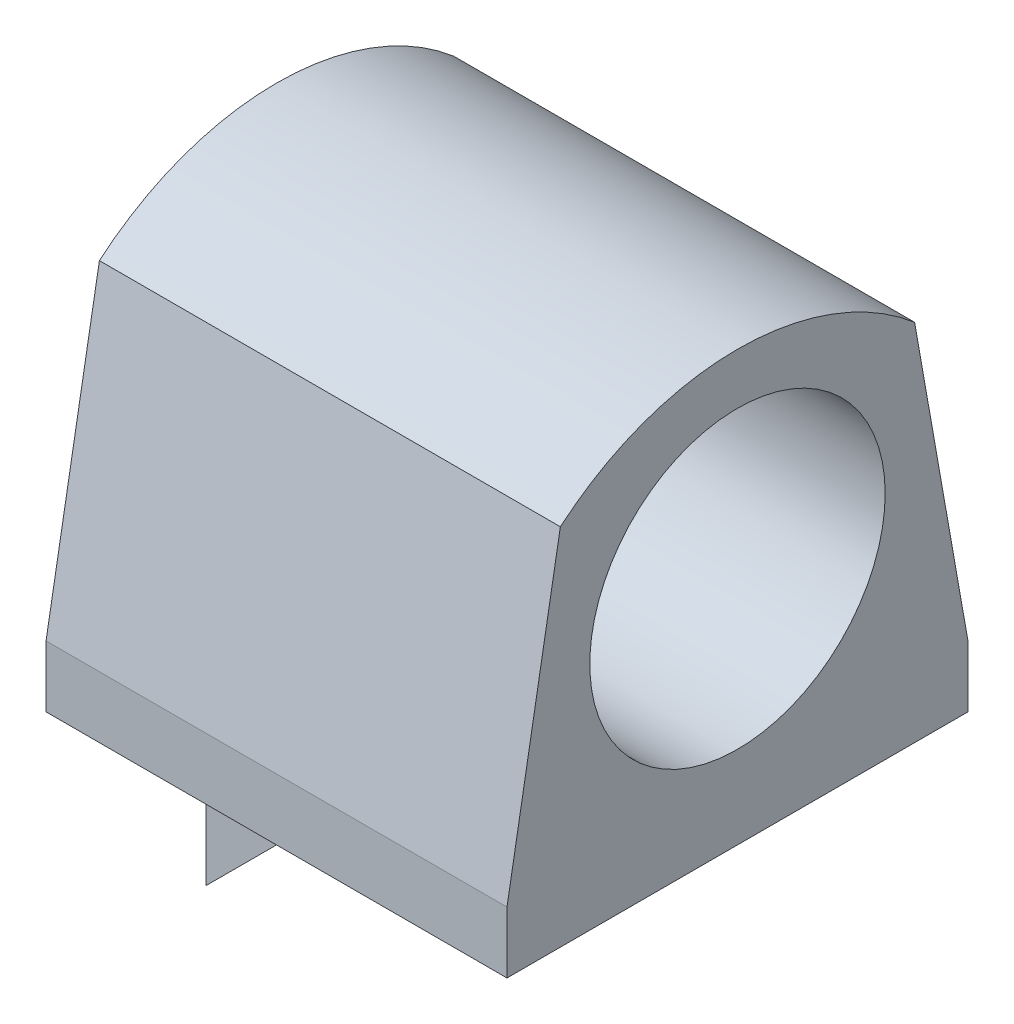
SolidWorks part; units mm, degrees
material "ABS"
ref_plane "Front Plane" through (0, 0, 0) normal (0, 0, 1) x (1, 0, 0)
ref_plane "Top Plane" through (0, 0, 0) normal (0, 1, 0) x (1, 0, 0)
ref_plane "Right Plane" through (0, 0, 0) normal (1, 0, 0) x (0, 0, -1)
sketch "Sketch2" plane through (0, 0, 0) normal (0, 1, 0) x (1, 0, 0)
  line L1 (-19.05, -19.05) -> (19.05, -19.05)
  line L2 (-19.05, -19.05) -> (-19.05, 19.05)
  line L3 (-19.05, 19.05) -> (19.05, 19.05)
  line L4 (19.05, -19.05) -> (19.05, 19.05)
  line L5 (-19.05, -19.05) -> (19.05, 19.05) construction
  line L6 (-19.05, 19.05) -> (19.05, -19.05) construction
  point P0 (0, 0)
  dimension "D1" = 38.1
  dimension "D2" = 38.1
extrude "Boss-Extrude1" add sketch "Sketch2" along normal blind 5.08
sketch "Sketch3" plane through (19.05, 0, 0) normal (1, 0, 0) x (0, 0, -1)
  line L0 (-19.05, 5.08) -> (-14.6393, 30.0941)
  line L1 (19.05, 5.08) -> (14.6393, 30.0941)
  line L3 (-19.05, 5.08) -> (19.05, 5.08) construction
  line L4 (19.05, 5.08) -> (-19.05, 5.08)
  arc A1 (-14.6393, 30.0941) -> (14.6393, 30.0941) centre (0, 12.91) cw
  dimension "D1" = 80
  dimension "D2" = 80
extrude "Boss-Extrude3" add sketch "Sketch3" along direction (1, 0, 0) on the side against the normal through all
sketch "Sketch5" plane through (19.05, 0, 0) normal (1, 0, 0) x (0, 0, -1)
  line L0 (-19.05, 0) -> (19.05, 0) construction
  circle A0 centre (0, 19.05) radius 12.2085
  dimension "D1" = 19.05
extrude "Cut-Extrude1" cut sketch "Sketch5" against normal through all
sketch "Sketch6" plane through (0, 0, 0) normal (0, -1, 0) x (-1, 0, 0)
  line L0 (19.05, 19.05) -> (19.05, -0.762)
  line L1 (19.05, 19.05) -> (19.05, -19.05) construction
  line L2 (19.05, -0.762) -> (19.05, -5.842)
  line L3 (19.05, -5.842) -> (0, -5.842)
  line L4 (0, -5.842) -> (0, -0.762)
  line L5 (0, -0.762) -> (19.05, -0.762)
  dimension "D1" = 19.812
  dimension "D2" = 5.08
  dimension "D3" = 19.05
ref_plane "Plane1" through (0, 0, 0.762) normal (0, 0, -1) x (-1, 0, 0)
sketch "Sketch7" plane through (0, 0, 0.762) normal (0, 0, -1) x (-1, 0, 0)
  line L0 (0, 0) -> (19.05, -19.05)
  line L1 (19.05, -19.05) -> (19.05, 0)
  line L2 (19.05, 0) -> (0, 0)
  point P3 (19.05, -11.5905)
extrude "Boss-Extrude4" add sketch "Sketch7" against normal up to vertex (5.08 mm away) up to point (-19.05, 0, 5.842)
